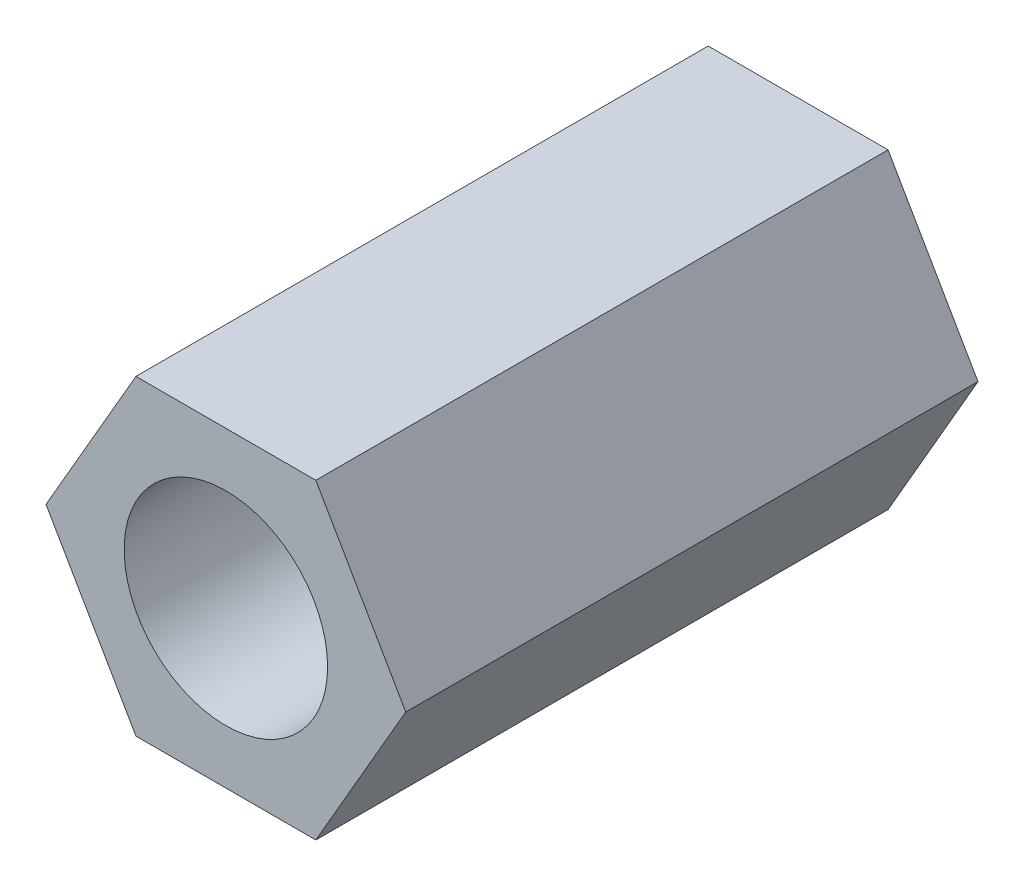
SolidWorks part; units mm, degrees
material "黄铜"
ref_plane "前视基准面" through (0, 0, 0) normal (0, 0, 1) x (1, 0, 0)
ref_plane "上视基准面" through (0, 0, 0) normal (0, 1, 0) x (1, 0, 0)
ref_plane "右视基准面" through (0, 0, 0) normal (1, 0, 0) x (0, 0, -1)
sketch "草图1" plane through (0, 0, 0) normal (0, 0, 1) x (1, 0, 0)
  line L1 (2.829, 0) -> (1.4145, 2.45)
  line L2 (1.4145, 2.45) -> (-1.4145, 2.45)
  line L3 (-1.4145, 2.45) -> (-2.829, 0)
  line L4 (-2.829, 0) -> (-1.4145, -2.45)
  line L5 (-1.4145, -2.45) -> (1.4145, -2.45)
  line L6 (1.4145, -2.45) -> (2.829, 0)
  circle A0 centre (0, 0) radius 1.6
  circle A1 centre (0, 0) radius 2.45 construction
  dimension "D1" = 3.2
  dimension "D2" = 4.9
extrude "凸台-拉伸1" add sketch "草图1" along normal blind 9
